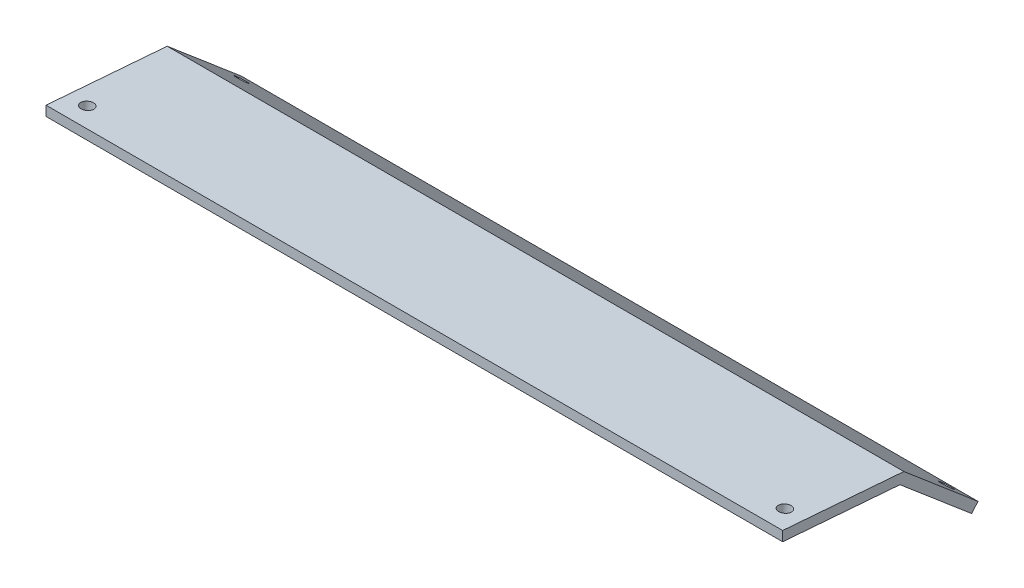
SolidWorks part; units mm, degrees
ref_plane "Front Plane" through (0, 0, 0) normal (0, 0, 1) x (1, 0, 0)
ref_plane "Top Plane" through (0, 0, 0) normal (0, 1, 0) x (1, 0, 0)
ref_plane "Right Plane" through (0, 0, 0) normal (1, 0, 0) x (0, 0, -1)
sketch "Sketch1" plane through (0, 0, 0) normal (1, 0, 0) x (0, 0, -1)
  line L7 (38.1697, -3.0031) -> (61.5101, -22.8106) construction
  line L8 (0, 0) -> (0, 3.1848)
  line L9 (0, 3.1848) -> (39.4417, 0.0816)
  line L10 (39.4417, 0.0816) -> (63.5645, -20.3898)
  line L11 (63.5645, -20.3898) -> (61.5101, -22.8106)
  line L12 (61.5101, -22.8106) -> (38.1697, -3.0031)
  line L13 (38.1697, -3.0031) -> (0, 0)
  arc A0 (60.9867, -25.0134) -> (61.9316, -23.5194) centre (60.6884, -23.7789) ccw construction
  arc A1 (60.9867, -25.0134) -> (61.5101, -22.8106) centre (60.6884, -23.7789) ccw construction
  dimension "D1" = 3.175
  dimension "D2" = 3.175
extrude "Boss-Extrude1" add sketch "Sketch1" along normal mid plane 239.7125
sketch "Sketch2" plane through (0, 3.1652, -0.249) normal (0, 0.9969, -0.0784) x (1, 0, 0)
  circle A0 centre (113.5062, 6.86) radius 2.032
  circle A1 centre (-113.5063, 6.86) radius 2.032
  dimension "D1" = 4.064
extrude "Cut-Extrude1" cut sketch "Sketch2" against normal through all
sketch "Sketch3" plane through (0, 19.5056, -16.5532) normal (0, 0.7625, -0.647) x (1, 0, 0)
  circle A0 centre (-113.5062, 53.403) radius 2.032
  circle A1 centre (113.5062, 56.578) radius 2.032
  dimension "D1" = 4.064
extrude "Cut-Extrude2" cut sketch "Sketch3" against normal blind 12.7
